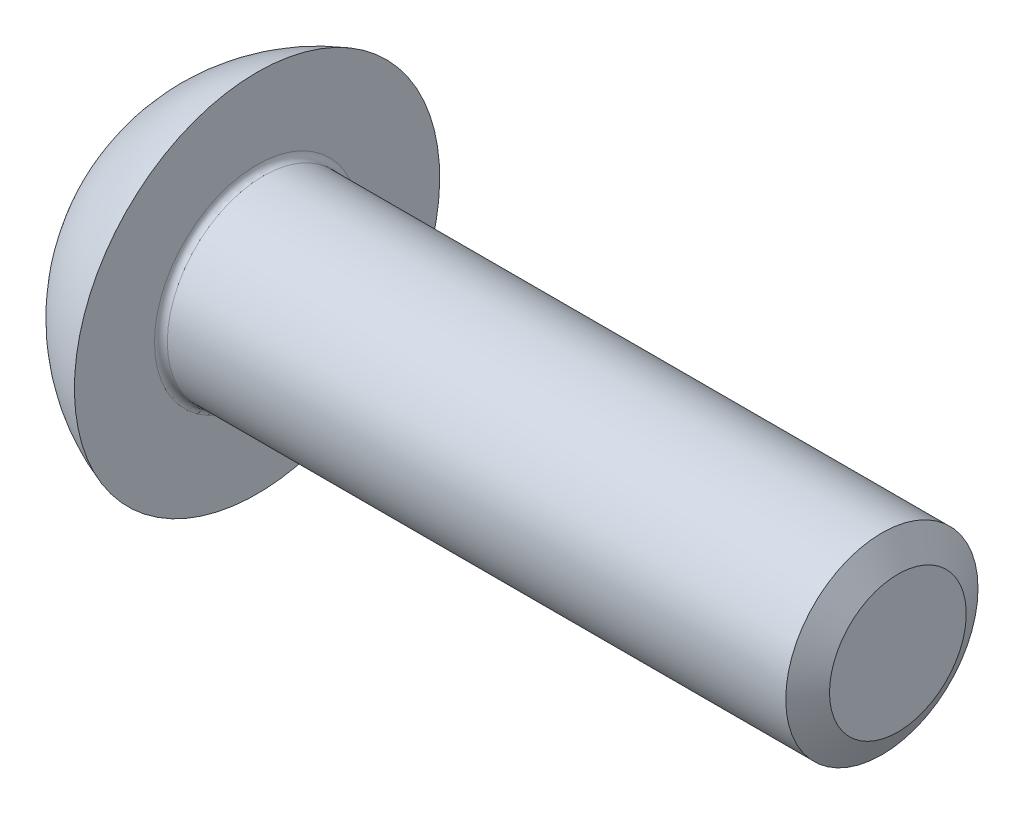
SolidWorks part; units mm, degrees
ref_plane "前视基准面" through (0, 0, 0) normal (0, 0, 1) x (1, 0, 0)
ref_plane "上视基准面" through (0, 0, 0) normal (0, 1, 0) x (1, 0, 0)
ref_plane "右视基准面" through (0, 0, 0) normal (1, 0, 0) x (0, 0, -1)
sketch "尺寸草图" plane through (0, 0, 0) normal (0, 0, 1) x (1, 0, 0)
  line L0 (0, 0) -> (10, 0) construction
  line L1 (10, 0) -> (10, 1.5) construction
  line L2 (10, 1.5) -> (9.5, 1.5) construction
  line L3 (0, 0) -> (0, 2.85) construction
  point P3 (1, 0)
  point P6 (10, 1.8)
  point P7 (0, 0.55)
  point P9 (1.65, 0)
  point P10 (1.75, 0)
  point P11 (10, 1)
  point P12 (2.79, 0)
  point P13 (2.99, 0)
  dimension "l" = 10
  dimension "d" = 3
  dimension "P" = 0.5
  dimension "a" = 1
  dimension "da" = 3.6
  dimension "dk" = 5.7
  dimension "e" = 2.3
  dimension "K" = 1.65
  dimension "r" = 0.1
  dimension "s" = 2
  dimension "t" = 1.04
  dimension "w" = 0.2
sketch "草图1" plane through (0, 0, 0) normal (0, 0, 1) x (1, 0, 0)
  line L0 (-11.65, 0) -> (0, 0) construction
  line L1 (0, 1.5) -> (-9.9, 1.5)
  line L2 (-10, 1.6) -> (-10, 2.85)
  line L3 (-11.65, 0) -> (-11.65, 1.5)
  line L4 (0, 1.5) -> (0, 0)
  line L5 (-11.65, 0) -> (0, 0)
  arc A0 (-10, 2.85) -> (-11.65, 1.5) centre (-9.0455, 0) ccw
  arc A1 (-9.9, 1.5) -> (-10, 1.6) centre (-9.9, 1.6) cw
  point P10 (-10, 1.5)
  dimension "r" = 0.1
  dimension "d" = 3
  dimension "dk" = 5.7
  dimension "k" = 1.65
  dimension "l" = 10
revolve "旋转1" add sketch "草图1" angle 360 about L0
cosmetic thread "装饰螺纹线1" parameters "D1"=9, "D2"=2.58
sketch "草图2" plane through (-11.65, 0, 0) normal (-1, 0, 0) x (0, 0, 1)
  line L1 (0, 1.1547) -> (-1, 0.5774)
  line L2 (-1, 0.5774) -> (-1, -0.5774)
  line L3 (-1, -0.5774) -> (0, -1.1547)
  line L4 (0, -1.1547) -> (1, -0.5774)
  line L5 (1, -0.5774) -> (1, 0.5774)
  line L6 (1, 0.5774) -> (0, 1.1547)
  circle A0 centre (0, 0) radius 1 construction
  dimension "s" = 2
extrude "切除-拉伸1" cut sketch "草图2" against normal blind 1.65
sketch "草图6" plane through (0, 0, 0) normal (0, 0, 1) x (1, 0, 0)
  line L0 (-10.61, 1.1547) -> (-10, 0)
  line L1 (-9.7, 1.1547) -> (-9.7, 0)
  line L2 (-9.7, 1.1547) -> (-10.61, 1.1547)
  line L3 (-11.65, 0) -> (-10, 0) construction
  line L4 (-9.7, 0) -> (-10, 0)
  line L5 (-11.65, 0) -> (-13.95, 0) construction
  dimension "t" = 1.04
  dimension "e-s" = 0.3
  dimension "k" = 1.65
  dimension "e" = 2.3
revolve "旋转2" add sketch "草图6" angle 360 about L3
sketch "草图7" plane through (0, 0, 0) normal (0, 0, 1) x (1, 0, 0)
  line L3 (-11.65, 1.1547) -> (-11.35, 0)
  line L4 (-11.65, 0) -> (-11.35, 0) construction
  line L7 (-11.65, 1.1547) -> (-11.65, 0)
  line L8 (-11.65, 0) -> (-11.35, 0)
  dimension "e-s" = 0.3
revolve "切除-旋转5" cut sketch "草图7" angle 360 about L4
sketch "草图4" plane through (0, 0, 0) normal (0, 0, 1) x (1, 0, 0)
  line L0 (-0.25, 1.5) -> (0, 1.067)
  line L1 (-0.25, 1.5) -> (0.25, 1.5)
  line L2 (0.25, 1.5) -> (0, 1.067)
  line L4 (0, -1.5) -> (0, 1.5) construction
  line L5 (-0.25, 0) -> (0.25, 0) construction
  dimension "d" = 1.5
  dimension "p" = 0.5
revolve "切除-旋转1" cut sketch "草图4" angle 360 about L5
ref_axis "基准轴1" through (-8.1887, 0, 0) along (1, 0, 0)
pattern_linear "阵列(线性)1" [suppressed] count 18 spacing 0.5 along (-1, 0, 0) of bodies 104
